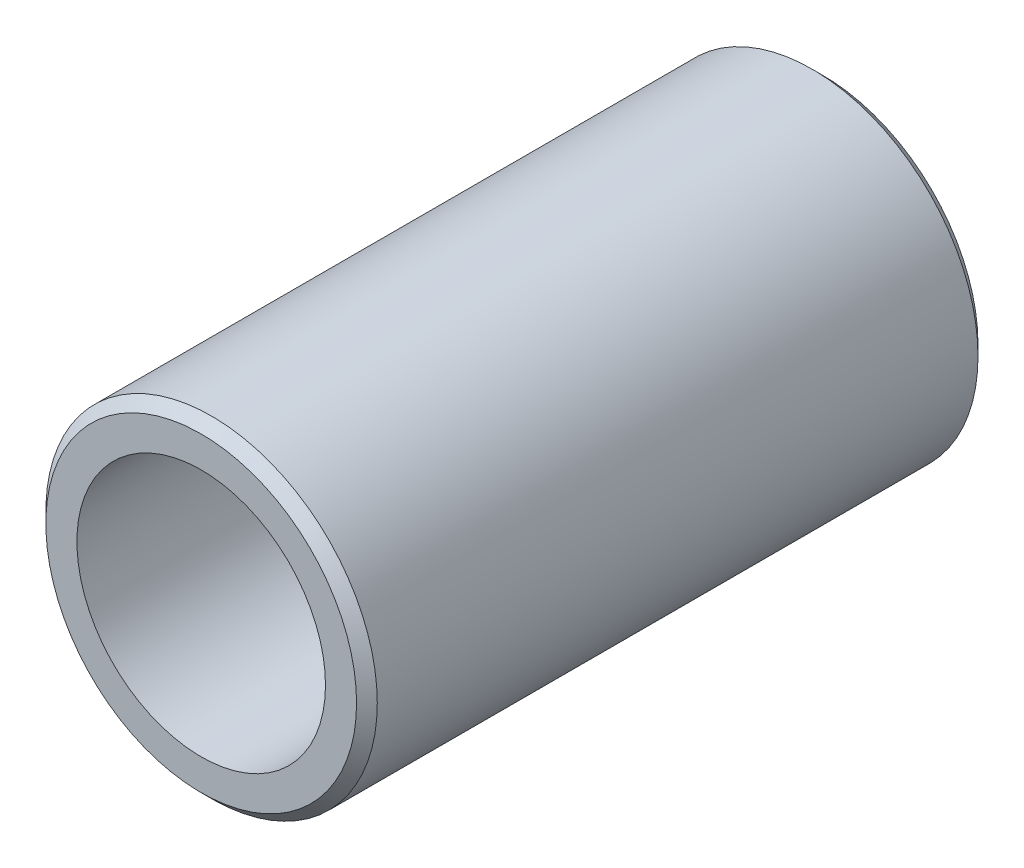
SolidWorks part; units mm, degrees
material "Brass"
ref_plane "Front Plane" through (0, 0, 0) normal (0, 0, 1) x (1, 0, 0)
ref_plane "Top Plane" through (0, 0, 0) normal (0, 1, 0) x (1, 0, 0)
ref_plane "Right Plane" through (0, 0, 0) normal (1, 0, 0) x (0, 0, -1)
sketch "Sketch1" plane through (0, 0, 0) normal (0, 0, 1) x (1, 0, 0)
  circle A0 centre (0, 0) radius 6
  dimension "D1" = 12
extrude "Extrude-Thin1" add sketch "Sketch1" along normal blind 30 thin thin type one direction wall 2
chamfer "Chamfer1" distance 0.5 angle 45 2 edges at (8, 0, 0) (8, 0, 30)
